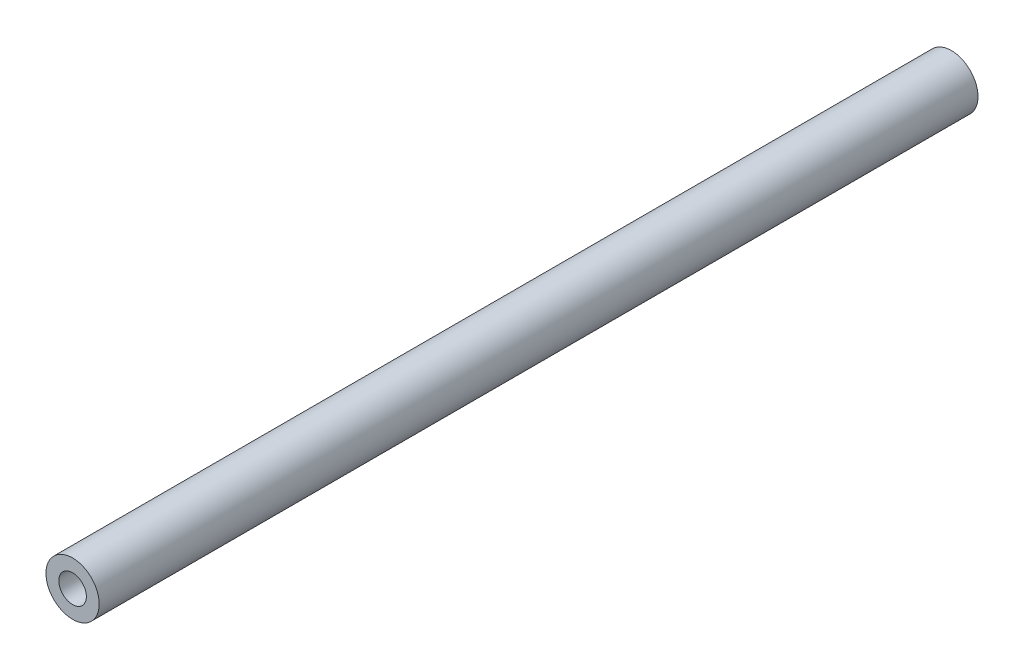
SolidWorks part; units mm, degrees
material "Plain Carbon Steel"
ref_plane "Front Plane" through (0, 0, 0) normal (0, 0, 1) x (1, 0, 0)
ref_plane "Top Plane" through (0, 0, 0) normal (0, 1, 0) x (1, 0, 0)
ref_plane "Right Plane" through (0, 0, 0) normal (1, 0, 0) x (0, 0, -1)
sketch "Sketch1" plane through (0, 0, 0) normal (0, 0, 1) x (1, 0, 0)
  circle A0 centre (0, 0) radius 5
  dimension "D1" = 10
extrude "Boss-Extrude1" add sketch "Sketch1" along normal blind 165
hole_wizard "#6 (0.204) Diameter Hole1" positions "Sketch2" profile "Sketch3" hole size "#6" standard "ANSI Inch"
sketch "Sketch2" plane through (0, 0, 0) normal (0, 0, -1) x (-1, 0, 0)
  point P0 (0, 0)
sketch "Sketch3" plane through (0, 0, 0) normal (1, 0, 0) x (0, 1, 0)
  line L0 (0, 0) -> (0, 31.5567)
  line L1 (0, 31.5567) -> (2.5908, 30)
  line L2 (2.5908, 30) -> (2.5908, 0)
  line L5 (2.5908, 0) -> (0, 0)
  line L10 (0, 31.5567) -> (-2.5908, 30) construction
  line L11 (0, -6.35) -> (0, 107.95) construction
  dimension "Hole Dia." = 5.1816
  dimension "Hole Depth" = 30
  dimension "Drill Angle" = 118
hole_wizard "#6 (0.204) Diameter Hole2" positions "Sketch4" profile "Sketch5" hole size "#6" standard "ANSI Inch"
sketch "Sketch4" plane through (0, 0, 165) normal (0, 0, 1) x (1, 0, 0)
  point P0 (0, 0)
sketch "Sketch5" plane through (0, 0, 165) normal (1, 0, 0) x (0, -1, 0)
  line L0 (0, 0) -> (0, 31.5567)
  line L1 (0, 31.5567) -> (2.5908, 30)
  line L2 (2.5908, 30) -> (2.5908, 0)
  line L5 (2.5908, 0) -> (0, 0)
  line L10 (0, 31.5567) -> (-2.5908, 30) construction
  line L11 (0, -6.35) -> (0, 107.95) construction
  dimension "Hole Dia." = 5.1816
  dimension "Hole Depth" = 30
  dimension "Drill Angle" = 118
